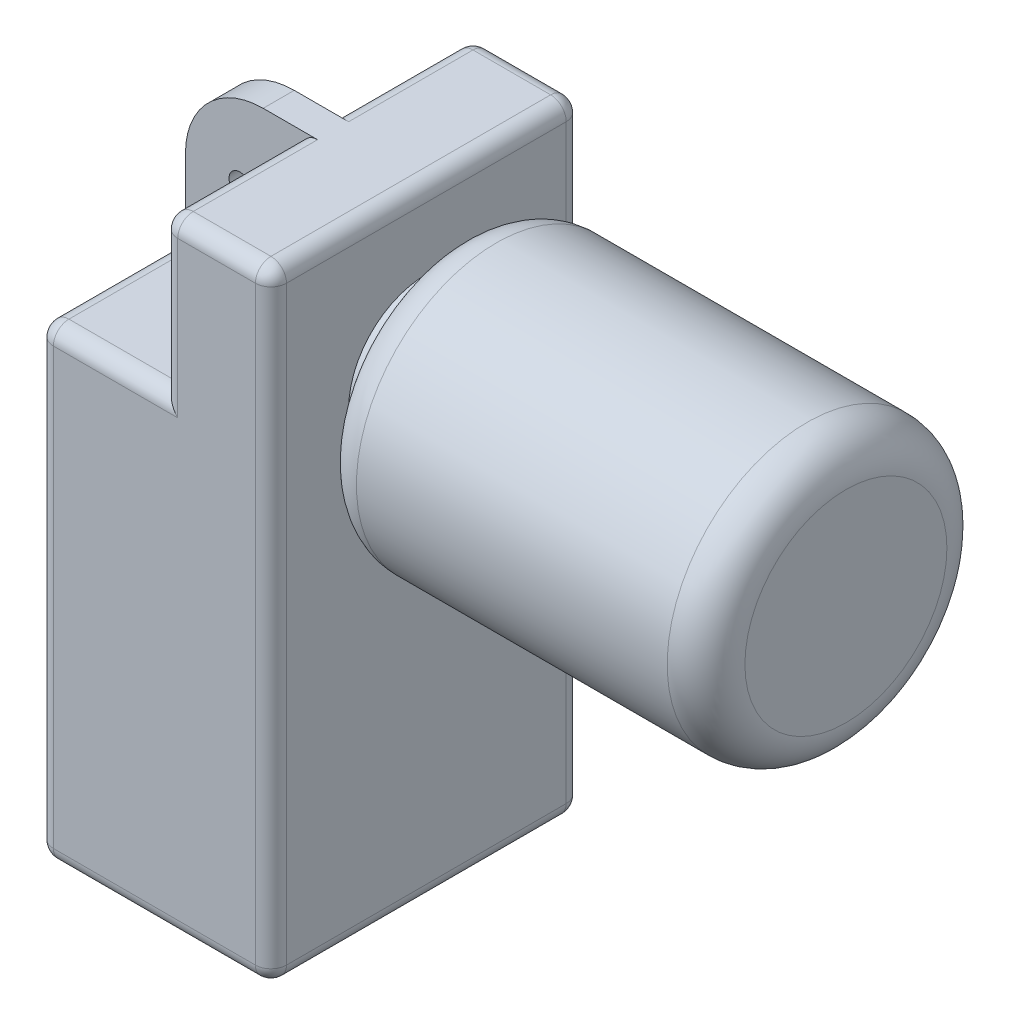
SolidWorks part; units mm, degrees
ref_plane "前视" through (0, 0, 0) normal (0, 0, 1) x (1, 0, 0)
ref_plane "上视" through (0, 0, 0) normal (0, 1, 0) x (1, 0, 0)
ref_plane "右视" through (0, 0, 0) normal (1, 0, 0) x (0, 0, -1)
sketch "草图1" plane through (0, 0, 0) normal (0, 0, 1) x (1, 0, 0)
  line L0 (-35, 0) -> (-35, -50)
  line L1 (-35, -50) -> (40, -50)
  line L2 (40, -50) -> (40, 50)
  line L3 (40, 50) -> (15, 50)
  arc A0 (-35, 0) -> (15, 50) centre (15, 0) cw
  circle A1 centre (0, 0) radius 7
  dimension "D6" = 14
  dimension "D1" = 50
  dimension "D2" = 100
  dimension "D3" = 35
  dimension "D4" = 40
  dimension "D5" = 50
extrude "凸台-拉伸1" add sketch "草图1" along normal blind 20
sketch "草图2" plane through (0, -50, 0) normal (0, -1, 0) x (-1, 0, 0)
  line L1 (40, -110) -> (-110, -110)
  line L2 (40, -110) -> (40, 90)
  line L3 (40, 90) -> (-110, 90)
  line L4 (-110, -110) -> (-110, 90)
  line L5 (-965, -10) -> (49035, -10) construction
  line L6 (35, -20) -> (35, 0) construction
  point P12 (35, -10)
  dimension "D1" = 200
  dimension "D2" = 150
  dimension "D3" = 100
  dimension "D4" = 5
extrude "凸台-拉伸2" add sketch "草图2" along normal blind 300
sketch "草图3" plane through (0, -50, 0) normal (0, 1, 0) x (1, 0, 0)
  line L0 (110, -110) -> (-40, -110) construction
  line L1 (110, 90) -> (40, 90)
  line L2 (110, 90) -> (110, -110)
  line L3 (110, -110) -> (40, -110)
  line L4 (40, 90) -> (40, -110)
  line L5 (40, -20) -> (40, 0) construction
extrude "凸台-拉伸3" add sketch "草图3" along normal blind 100
sketch "草图4" plane through (110, 0, 0) normal (1, 0, 0) x (0, 0, -1)
  line L0 (-10, -1350) -> (-10, 48650) construction
  line L1 (90, -350) -> (-110, -350) construction
  line L2 (-110, 50) -> (90, 50) construction
  circle A0 centre (-10, -50) radius 50
  point P7 (-10, -350)
  dimension "D1" = 100
  dimension "D2" = 100
extrude "凸台-拉伸4" add sketch "草图4" along normal blind 20
sketch "草图5" plane through (130, 0, 0) normal (1, 0, 0) x (0, 0, -1)
  circle A0 centre (-10, -50) radius 90
  circle A1 centre (-10, -50) radius 50 construction
  dimension "D1" = 180
extrude "凸台-拉伸5" add sketch "草图5" along normal blind 250
fillet "圆角1" radius 25 2 edges at (130, -50, -80) (380, -50, -80)
fillet "圆角2" radius 10 18 edges at (75, 50, 110) (40, 0, 110) (-40, -50, 10) (-40, -200, 110) (110, -150, 110) (110, -350, 10) (35, -350, 110) (-40, -350, 10) (0, -50, -90) (40, 0, -90) (75, 50, -90) (-40, -200, -90) (35, -350, -90) (110, 50, 10) (110, -150, -90) (40, 50, -45) (40, 50, 65) (0, -50, 110)
sketch "草图6" plane through (-40, 0, 0) normal (-1, 0, 0) x (0, 0, 1)
  line L0 (10, -1000) -> (10, 49000) construction
  line L1 (20, 0) -> (0, 0) construction
  line L2 (20, 50) -> (100, 50) construction
  circle A0 centre (10, -224) radius 25.5
  point P5 (10, 0)
  dimension "D2" = 51
  dimension "D1" = 274
extrude "切除-拉伸1" cut sketch "草图6" against normal blind 100
